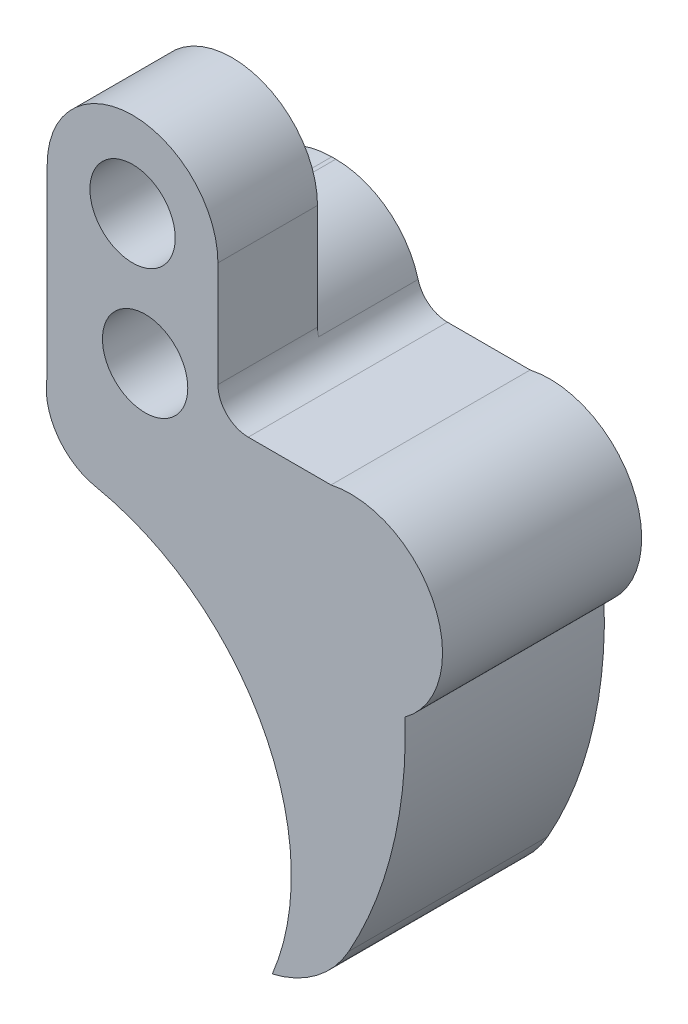
SolidWorks part; units mm, degrees
material "Plain Carbon Steel"
ref_plane "Front" through (0, 0, 0) normal (0, 0, 1) x (1, 0, 0)
ref_plane "Top" through (0, 0, 0) normal (0, 1, 0) x (1, 0, 0)
ref_plane "Right" through (0, 0, 0) normal (1, 0, 0) x (0, 0, -1)
sketch "Sketch1" plane through (0, 0, 0) normal (0, 0, 1) x (1, 0, 0)
  line L0 (-7.3793, 6.5541) -> (-7.3793, 12.9923)
  line L1 (-1.3793, 12.9923) -> (-1.3793, 9.2882)
  line L2 (-0.3132, 8.2221) -> (2.5963, 8.2221)
  arc A0 (0.5317, -7.6979) -> (-5.6526, 4.0272) centre (-7.3793, -4.377) ccw
  arc A1 (3.2188, -5.6674) -> (5.1964, 2.4573) centre (-10.3613, 1.9412) ccw
  arc A2 (-0.3132, 8.2221) -> (-1.3793, 9.2882) centre (-0.3132, 9.2882) cw
  arc A3 (-1.3793, 12.9923) -> (-7.3793, 12.9923) centre (-4.3793, 12.9923) ccw
  arc A5 (2.5963, 8.2221) -> (5.1964, 2.4573) centre (3.2831, 5.0631) cw
  arc A6 (-7.3793, 6.5541) -> (-5.6526, 4.0272) centre (-5.2389, 6.1633) ccw
  arc A7 (3.2188, -5.6674) -> (0.5317, -7.6979) centre (-0.4417, -3.6165) cw
  dimension "D1" = 6
extrude "Boss-Extrude1" add sketch "Sketch1" along normal blind 3.5 and the other way blind 3.5
sketch "Sketch5" plane through (0, 0, 0) normal (0, 0, 1) x (1, 0, 0)
  circle A0 centre (-3.9386, 8.6517) radius 1.5
  dimension "D1" = 3
sketch "Sketch6" plane through (0, 0, 3.5) normal (0, 0, 1) x (1, 0, 0)
  circle A0 centre (-4.3793, 12.9923) radius 1.5
  dimension "D1" = 3
extrude "Cut-Extrude1" cut sketch "Sketch6" against normal through all
sketch "Sketch7" plane through (0, 0, 0) normal (1, 0, 0) x (0, 0, -1)
  line L0 (0, -1000) -> (0, 49000) construction
  line L2 (0, 18.1036) -> (4.0341, 18.1036)
  line L3 (0, 18.1036) -> (0, 11.2215)
  line L4 (0, 11.2215) -> (4.0341, 11.2215)
  line L5 (4.0341, 18.1036) -> (4.0341, 11.2215)
extrude "Cut-Extrude2" cut sketch "Sketch7" against normal through all
fillet "Fillet1" radius 3 2 edges at (-7.3793, 11.2215, -1.75) (-1.3793, 11.2215, -1.75)
extrude "Cut-Extrude3" cut sketch "Sketch5" against normal through all and the other way through all
